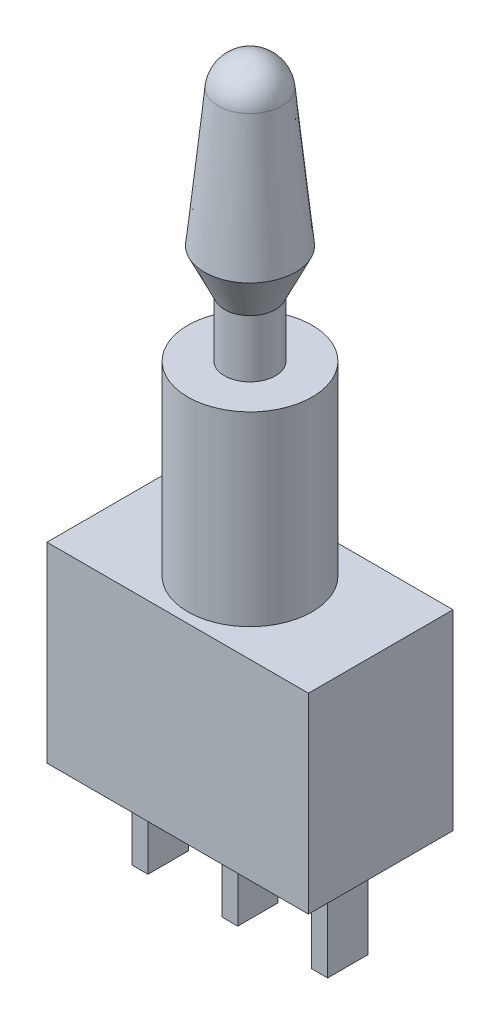
SolidWorks part; units mm, degrees
ref_plane "Front Plane" through (0, 0, 0) normal (0, 0, 1) x (1, 0, 0)
ref_plane "Top Plane" through (0, 0, 0) normal (0, 1, 0) x (1, 0, 0)
ref_plane "Right Plane" through (0, 0, 0) normal (1, 0, 0) x (0, 0, -1)
sketch "Sketch1" plane through (0, 0, 0) normal (0, 1, 0) x (1, 0, 0)
  line L1 (-6.15, -3.4) -> (6.15, -3.4)
  line L2 (-6.15, -3.4) -> (-6.15, 3.4)
  line L3 (-6.15, 3.4) -> (6.15, 3.4)
  line L4 (6.15, -3.4) -> (6.15, 3.4)
  line L5 (-6.15, -3.4) -> (6.15, 3.4) construction
  line L6 (-6.15, 3.4) -> (6.15, -3.4) construction
  point P0 (0, 0)
  dimension "D1" = 12.3
  dimension "D2" = 6.8
extrude "Boss-Extrude1" add sketch "Sketch1" along normal blind 9
sketch "Sketch2" plane through (0, 9, 0) normal (0, 1, 0) x (1, 0, 0)
  circle A0 centre (0, 0) radius 2.925
  dimension "D1" = 5.85
extrude "Boss-Extrude2" add sketch "Sketch2" along normal blind 8.75
sketch "Sketch3" plane through (0, 0, 0) normal (0, 0, 1) x (1, 0, 0)
  line L0 (0, -982.25) -> (0, 49017.75) construction
  line L1 (2.925, 17.75) -> (-2.925, 17.75) construction
  line L2 (0, 17.75) -> (1.2, 17.75)
  line L3 (1.2, 17.75) -> (1.2, 20.45)
  line L4 (1.2, 20.45) -> (2.15, 22.45)
  line L5 (2.15, 22.45) -> (1.5, 28.8937)
  line L6 (0, 30.25) -> (0, 17.75)
  arc A0 (1.5, 28.8937) -> (0, 30.25) centre (0, 28.7424) ccw
  point P5 (0, 17.75)
  point P12 (0, 0)
  dimension "D1" = 2.4
  dimension "D2" = 4.3
  dimension "D3" = 3
  dimension "D4" = 2.7
  dimension "D5" = 2
  dimension "D6" = 12.5
revolve "Revolve1" add sketch "Sketch3" angle 360 about L0
sketch "Sketch4" plane through (0, 0, 0) normal (0, -1, 0) x (1, 0, 0)
  line L0 (-4.6, 0.95) -> (4.6, 0.95) construction
  line L1 (-0.375, -0.95) -> (0.375, -0.95)
  line L2 (-0.375, -0.95) -> (-0.375, 0.95)
  line L3 (-0.375, 0.95) -> (0.375, 0.95)
  line L4 (0.375, -0.95) -> (0.375, 0.95)
  line L5 (-0.375, -0.95) -> (0.375, 0.95) construction
  line L6 (-0.375, 0.95) -> (0.375, -0.95) construction
  line L7 (-4.6, -0.95) -> (-3.85, -0.95)
  line L8 (-4.6, -0.95) -> (-4.6, 0.95)
  line L9 (-4.6, 0.95) -> (-3.85, 0.95)
  line L10 (-3.85, -0.95) -> (-3.85, 0.95)
  line L11 (-4.6, -0.95) -> (-3.85, 0.95) construction
  line L12 (-4.6, 0.95) -> (-3.85, -0.95) construction
  line L13 (3.85, -0.95) -> (4.6, -0.95)
  line L14 (3.85, -0.95) -> (3.85, 0.95)
  line L15 (3.85, 0.95) -> (4.6, 0.95)
  line L16 (4.6, -0.95) -> (4.6, 0.95)
  line L17 (3.85, -0.95) -> (4.6, 0.95) construction
  line L18 (3.85, 0.95) -> (4.6, -0.95) construction
  line L19 (-3.85, -0.95) -> (-0.375, -0.95) construction
  line L20 (0.375, -0.95) -> (3.85, -0.95) construction
  point P0 (0, 0)
  point P6 (-4.225, 0)
  point P11 (4.225, 0)
  dimension "D1" = 0.75
  dimension "D2" = 1.9
  dimension "D3" = 9.2
extrude "Boss-Extrude3" add sketch "Sketch4" along normal blind 4.6
